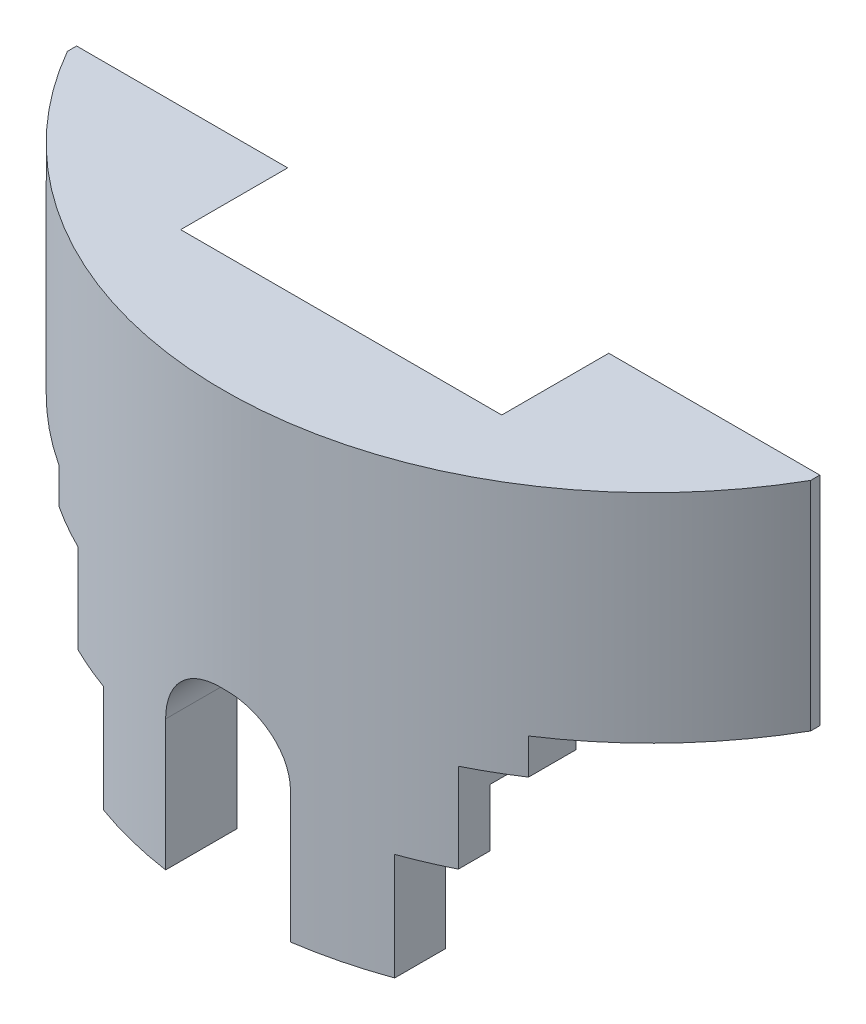
SolidWorks part; units mm, degrees
ref_plane "Front Plane" through (0, 0, 0) normal (0, 0, 1) x (1, 0, 0)
ref_plane "Top Plane" through (0, 0, 0) normal (0, 1, 0) x (1, 0, 0)
ref_plane "Right Plane" through (0, 0, 0) normal (1, 0, 0) x (0, 0, -1)
sketch "Sketch1" plane through (0, 0, 0) normal (0, 1, 0) x (1, 0, 0)
  line L0 (-62.5, -34.2) -> (-62.5, -35.7456)
  line L1 (-62.5, -34.2) -> (62.5, -34.2)
  line L2 (62.5, -34.2) -> (62.5, -35.7456)
  arc A0 (-62.5, -35.7456) -> (62.5, -35.7456) centre (0, 0) ccw
  dimension "D1" = 144
  dimension "D2" = 125
  dimension "D3" = 34.2
extrude "Boss-Extrude1" add sketch "Sketch1" against normal blind 36.5
sketch "Sketch2" plane through (0, -36.5, 0) normal (0, -1, 0) x (1, 0, 0)
  line L0 (-39.5, 60.1976) -> (-39.5, 34.2)
  line L1 (62.5, 34.2) -> (-62.5, 34.2) construction
  line L2 (-39.5, 34.2) -> (39.5, 34.2)
  line L3 (39.5, 34.2) -> (39.5, 60.1976)
  arc A0 (62.5, 35.7456) -> (-62.5, 35.7456) centre (0, 0) ccw construction
  arc A1 (-39.5, 60.1976) -> (39.5, 60.1976) centre (0, 0) cw
  line M2 (-62.5, 34.2) -> (62.5, 34.2)
  arc M4 (62.5, 35.7456) -> (-62.5, 35.7456) centre (0, 0) ccw
  dimension "D1" = 79
extrude "Boss-Extrude2" add sketch "Sketch2" along normal blind 6 contours L3 L0 M2 M4 region at (0, -36.5, 51.3794)
sketch "Sketch3" plane through (0, -42.5, 0) normal (0, -1, 0) x (1, 0, 0)
  line L0 (-32, 64.4981) -> (-32, 34.2)
  line L1 (-39.5, 34.2) -> (39.5, 34.2) construction
  line L2 (-32, 34.2) -> (32, 34.2)
  line L3 (32, 34.2) -> (32, 64.4981)
  arc A0 (39.5, 60.1976) -> (-39.5, 60.1976) centre (0, 0) ccw construction
  arc A1 (32, 64.4981) -> (-32, 64.4981) centre (0, 0) ccw
  dimension "D1" = 64
extrude "Boss-Extrude3" add sketch "Sketch3" along normal blind 15
sketch "Sketch4" plane through (0, -57.5, 0) normal (0, -1, 0) x (1, 0, 0)
  line L0 (-24.5, 34.2) -> (-24.5, 67.7034)
  line L1 (-32, 34.2) -> (32, 34.2) construction
  line L2 (-24.5, 34.2) -> (24.5, 34.2)
  line L3 (24.5, 34.2) -> (24.5, 67.7034)
  arc A0 (32, 64.4981) -> (-32, 64.4981) centre (0, 0) ccw construction
  arc A1 (-24.5, 67.7034) -> (24.5, 67.7034) centre (0, 0) cw
  dimension "D1" = 49
extrude "Boss-Extrude4" add sketch "Sketch4" along normal blind 18
sketch "Sketch7" plane through (0, 0, 34.2) normal (0, 0, -1) x (-1, 0, 0)
  line L0 (0, -75.5) -> (0, -53.5) construction
  line L1 (24.5, -75.5) -> (-24.5, -75.5) construction
  line L2 (-32.5, -53.5) -> (-32.5, -86)
  line L3 (-32.5, -86) -> (32.5, -86)
  line L4 (32.5, -86) -> (32.5, -53.5)
  arc A0 (32.5, -53.5) -> (-32.5, -53.5) centre (0, -53.5) ccw
  dimension "D2" = 65
  dimension "D1" = 22
extrude "Cut-Extrude2" cut sketch "Sketch7" against normal blind 25
sketch "Sketch5" plane through (0, -75.5, 0) normal (0, -1, 0) x (1, 0, 0)
  line L0 (-24.5, 34.2) -> (24.5, 34.2) construction
  line L1 (-10.5, 34.2) -> (10.5, 34.2)
  line L2 (-10.5, 34.2) -> (-10.5, 72)
  line L3 (-10.5, 72) -> (10.5, 72)
  line L4 (10.5, 34.2) -> (10.5, 72)
  arc A0 (24.5, 67.7034) -> (-24.5, 67.7034) centre (0, 0) ccw construction
  point P6 (0, 72)
  point P10 (0, 72)
  dimension "D1" = 21
extrude "Cut-Extrude1" cut sketch "Sketch5" against normal blind 32
fillet "Fillet1" radius 10 2 edges at (-10.5, -43.5, 65.2151) (10.5, -43.5, 65.2151)
sketch "Sketch8" plane through (0, 0, 34.2) normal (0, 0, -1) x (-1, 0, 0)
  line L0 (-27, -22) -> (27, -22) construction
  line L1 (-27, 0) -> (27, 0)
  line L2 (-27, -44) -> (27, -44)
  line L3 (-62.5, 0) -> (62.5, 0) construction
  arc A0 (-27, 0) -> (-27, -44) centre (-27, -22) ccw
  arc A1 (27, -44) -> (27, 0) centre (27, -22) ccw
  point P2 (0, -22)
  point P10 (0, 0)
  dimension "D1" = 22
  dimension "D2" = 54
extrude "Cut-Extrude3" cut sketch "Sketch8" against normal blind 18
sketch "Sketch9" plane through (0, 0, 34.2) normal (0, 0, -1) x (-1, 0, 0)
  line L1 (-43.2673, -38.5701) -> (43.5558, -38.5701)
  line L2 (-43.2673, -38.5701) -> (-43.2673, -49.7953)
  line L3 (-43.2673, -49.7953) -> (43.5558, -49.7953)
  line L4 (43.5558, -38.5701) -> (43.5558, -49.7953)
extrude "Cut-Extrude4" cut sketch "Sketch9" against normal up to surface (18 mm away) up to face at (0, -33.5816, 52.2)
equation "\"smallPulleyTeeth\"= 30"
equation "\"largePulleyTeeth\"= 30"
equation "\"eighthThick\"= 3.0mm"
equation "\"sixteenthThick\" = 1.7mm"
equation "\"quarterThick\"=6.0mm"
equation "\"OD\" = 145mm"
equation "\"puckAngle\" = 60.5deg"
equation "\"puckDiam\" = 76.5mm"
equation "\"puckDist\" = 85mm"
equation "\"scoopFillet\" = 5mm"
equation "\"axlePress\" = 5.9mm"
equation "\"press\" = 0.2mm"
equation "\"wheelClear\" = 0.3mm"
equation "\"10-32clear\" = 4.8mm"
equation "\"10-32tap\" = 4.45mm"
equation "\"6-32clear\" = 3.3mm"
equation "\"8-32clear\" = 4.0mm"
equation "\"4-40clear\" = 3.0mm"
equation "\"wheelHeight\" = 22mm"
equation "\"wheelWell\" = 65mm"
equation "\"ledSmall\" = 3.1mm"
equation "\"ledLarge\" = 4.2mm"
equation "\"ledLength\" = 4.2mm"
equation "\"4-40close\" = 2.7mm"
equation "\"4-40nutThick\" = 2.2mm"
equation "\"4-40nutWidth\" = 6.2mm"
equation "\"4-40insertHeight\" = 3.5mm"
equation "\"4-40insert\" = 4mm"
equation "\"D1@Sketch1\"=\"OD\"-1"
